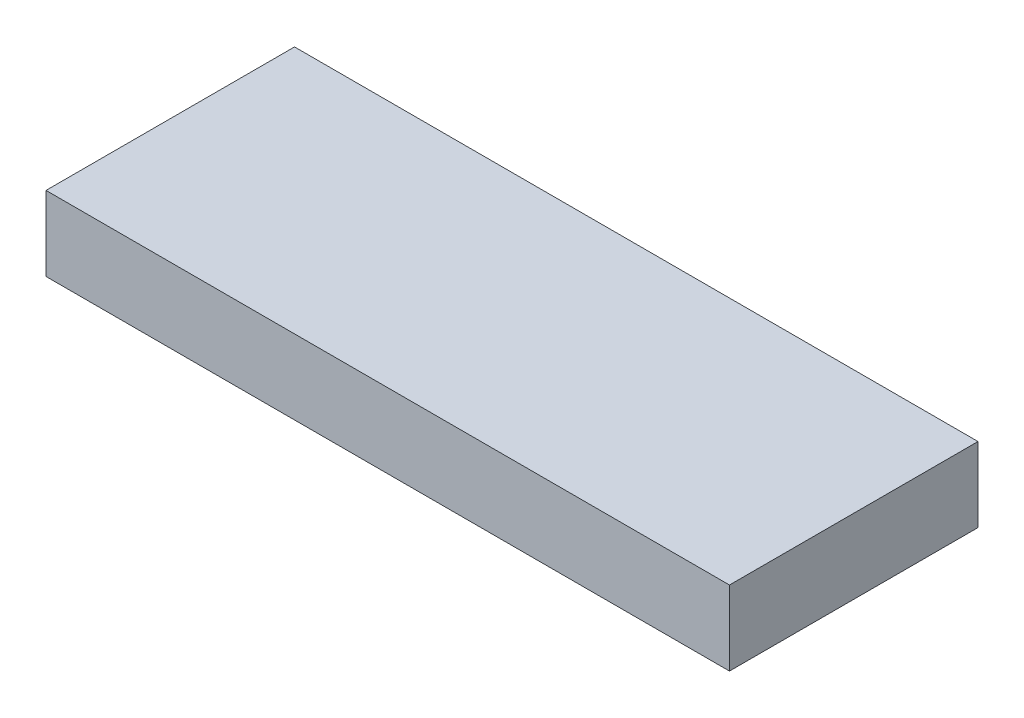
SolidWorks part; units mm, degrees
material "Maple"
ref_plane "Front Plane" through (0, 0, 0) normal (0, 0, 1) x (1, 0, 0)
ref_plane "Top Plane" through (0, 0, 0) normal (0, 1, 0) x (1, 0, 0)
ref_plane "Right Plane" through (0, 0, 0) normal (1, 0, 0) x (0, 0, -1)
sketch "Sketch1" plane through (0, 0, 0) normal (0, 1, 0) x (1, 0, 0)
  line L1 (-27.5, 10) -> (27.5, 10)
  line L2 (-27.5, 10) -> (-27.5, -10)
  line L3 (-27.5, -10) -> (27.5, -10)
  line L4 (27.5, 10) -> (27.5, -10)
  line L5 (-27.5, 10) -> (27.5, -10) construction
  line L6 (-27.5, -10) -> (27.5, 10) construction
  point P0 (0, 0)
  dimension "D1" = 55
  dimension "D2" = 20
extrude "Boss-Extrude1" add sketch "Sketch1" along normal blind 6
ref_plane "Plane1" through (0, 3, 0) normal (0, 1, 0) x (1, 0, 0)
